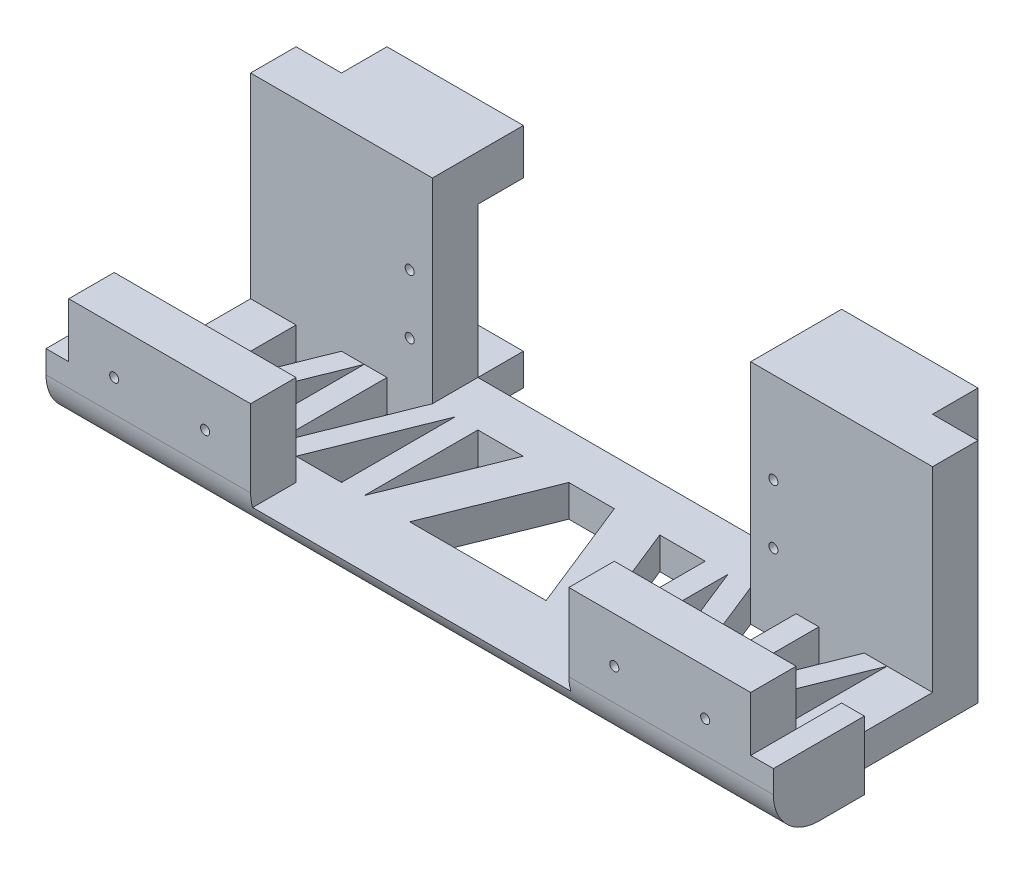
SolidWorks part; units mm, degrees
ref_plane "Plan de face" through (0, 0, 0) normal (0, 0, 1) x (1, 0, 0)
ref_plane "Plan de dessus" through (0, 0, 0) normal (0, 1, 0) x (1, 0, 0)
ref_plane "Plan de droite" through (0, 0, 0) normal (1, 0, 0) x (0, 0, -1)
sketch "Esquisse2" plane through (0, 0, 0) normal (0, 0, 1) x (1, 0, 0)
  line L0 (-161.1414, -90.4642) -> (-121.1414, -90.4642)
  line L1 (-161.1414, -90.4642) -> (-161.1414, -140.4642)
  line L2 (-121.1414, -90.4642) -> (-121.1414, -140.4642)
  line L3 (-161.1414, -140.4642) -> (-121.1414, -140.4642)
  line L4 (-121.1414, 19.5358) -> (-121.1414, -100.4642) construction
  line L5 (-11.1414, -90.4642) -> (-51.1414, -90.4642)
  line L6 (-11.1414, -90.4642) -> (-11.1414, -140.4642)
  line L7 (-51.1414, -90.4642) -> (-51.1414, -140.4642)
  line L8 (-11.1414, -140.4642) -> (-51.1414, -140.4642)
  line L9 (-51.1414, 19.5358) -> (-51.1414, -100.4642) construction
  line L11 (-121.1414, -133.4642) -> (-51.1414, -133.4642)
  line L12 (-121.1414, -140.4642) -> (-51.1414, -140.4642)
  line L13 (-51.1414, -133.4642) -> (-51.1414, -140.4642)
  line L14 (-136.1414, -133.4642) -> (-36.1414, -133.4642) construction
  line L15 (-21.1414, -140.4642) -> (-11.1414, -140.4642) construction
  line L16 (-151.1414, -90.4642) -> (-171.1414, -90.4642) construction
  line L17 (-1.1414, -90.4642) -> (-21.1414, -90.4642) construction
  line M10 (-51.1414, -100.4642) -> (-51.1414, 19.5358)
  line M16 (-121.1414, 19.5358) -> (-121.1414, -100.4642)
  line M17 (-121.1414, -100.4642) -> (-136.1414, -100.4642)
  line M18 (-136.1414, -100.4642) -> (-136.1414, -133.4642)
  line M19 (-136.1414, -133.4642) -> (-36.1414, -133.4642)
  line M20 (-36.1414, -133.4642) -> (-36.1414, -100.4642)
  line M21 (-36.1414, -100.4642) -> (-51.1414, -100.4642)
  circle M38 centre (-46.1414, -123.4642) radius 1
  circle M39 centre (-46.1414, -110.4642) radius 1
  circle M42 centre (-126.1414, -123.4642) radius 1
  circle M45 centre (-126.1414, -110.4642) radius 1
extrude "Boss.-Extru.1" add sketch "Esquisse2" along normal blind 10 contours L1 L3 L2 L0 M19 M18 M17 M16 | L2 M17 M18 M19 M42 M45 | L13 L2 L12 M19 | L7 M21 M19 M20 M38 M39 | L8 L6 L5 L7 M10 M21 M20 M19 region at (-145.2527, -114.9708, 0) region at (-128.6736, -116.9642, 0) region at (-86.1414, -136.9642, 0) region at (-27.0301, -114.9708, 0) region at (-43.6093, -116.9642, 0)
sketch "Esquisse3" plane through (0, 0, 10) normal (0, 0, 1) x (1, 0, 0)
  line L0 (-161.1414, -140.4642) -> (-161.1414, -133.4642)
  line L1 (-161.1414, -140.4642) -> (-11.1414, -140.4642)
  line L2 (-161.1414, -133.4642) -> (-11.1414, -133.4642)
  line L3 (-11.1414, -140.4642) -> (-11.1414, -133.4642)
  line L5 (-11.1414, -90.4642) -> (-11.1414, -140.4642) construction
  line L6 (-121.1414, -133.4642) -> (-51.1414, -133.4642) construction
  line L7 (-161.1414, -90.4642) -> (-161.1414, -140.4642) construction
  line L8 (-226.1414, -140.4642) -> (-161.1414, -140.4642) construction
extrude "Boss.-Extru.2" add sketch "Esquisse3" along normal blind 40
sketch "Esquisse4" plane through (0, 0, 50) normal (0, 0, 1) x (1, 0, 0)
  line L0 (-161.1414, -133.4642) -> (-161.1414, -113.4642)
  line L1 (-161.1414, -133.4642) -> (-121.1414, -133.4642)
  line L2 (-161.1414, -113.4642) -> (-121.1414, -113.4642)
  line L3 (-121.1414, -133.4642) -> (-121.1414, -113.4642)
  line L4 (-11.1414, -133.4642) -> (-11.1414, -113.4642)
  line L5 (-11.1414, -133.4642) -> (-51.1414, -133.4642)
  line L6 (-11.1414, -113.4642) -> (-51.1414, -113.4642)
  line L7 (-51.1414, -133.4642) -> (-51.1414, -113.4642)
  line L8 (-161.1414, -140.4642) -> (-161.1414, -125.4642)
  line L9 (-161.1414, -140.4642) -> (-166.1414, -140.4642)
  line L10 (-161.1414, -125.4642) -> (-166.1414, -125.4642)
  line L11 (-166.1414, -140.4642) -> (-166.1414, -125.4642)
  line L12 (-11.1414, -140.4642) -> (-11.1414, -125.4642)
  line L13 (-11.1414, -140.4642) -> (-6.1414, -140.4642)
  line L14 (-11.1414, -125.4642) -> (-6.1414, -125.4642)
  line L15 (-6.1414, -140.4642) -> (-6.1414, -125.4642)
  circle A0 centre (-151.1414, -123.4642) radius 1
  circle A1 centre (-131.1414, -123.4642) radius 1
  circle A2 centre (-41.1414, -123.4642) radius 1
  circle A3 centre (-21.1414, -123.4642) radius 1
  line M10 (-11.1414, -140.4642) -> (-11.1414, -133.4642)
  line M11 (-11.1414, -133.4642) -> (-161.1414, -133.4642)
  line M12 (-161.1414, -133.4642) -> (-161.1414, -140.4642)
  dimension "D13" = 2
  dimension "D14" = 2
  dimension "D19" = 2
  dimension "D20" = 2
  dimension "D1" = 40
  dimension "D2" = 20
  dimension "D3" = 40
  dimension "D4" = 20
  dimension "D5" = 15
  dimension "D6" = 5
  dimension "D7" = 15
  dimension "D8" = 5
  dimension "D9" = 10
  dimension "D10" = 10
  dimension "D11" = 10
  dimension "D12" = 10
  dimension "D15" = 10
  dimension "D16" = 10
  dimension "D17" = 10
  dimension "D18" = 10
extrude "Boss.-Extru.3" add sketch "Esquisse4" against normal blind 20 contours L7 L4 L6 M11 | L13 L15 L14 L4 M10 | L11 L9 L0 L10 M12 | L3 L2 L0 M11 region at (-163.6414, -132.9642, 50) region at (-141.1414, -123.4642, 50) region at (-31.1414, -123.4642, 50) region at (-8.6414, -132.9642, 50)
sketch "Esquisse5" plane through (0, -140.4642, 0) normal (0, -1, 0) x (1, 0, 0)
  line L18 (-151.1414, 35) -> (-151.1414, 10)
  line L19 (-151.1414, 10) -> (-141.1414, 10)
  line L20 (-141.1414, 10) -> (-151.1414, 35)
  line L21 (-146.1414, 35) -> (-136.1414, 10)
  line L22 (-136.1414, 10) -> (-136.1414, 35)
  line L23 (-136.1414, 35) -> (-146.1414, 35)
  line L24 (-131.1414, 35) -> (-131.1414, 10)
  line L25 (-131.1414, 10) -> (-121.1414, 10)
  line L26 (-121.1414, 10) -> (-131.1414, 35)
  line L27 (-126.1414, 35) -> (-116.1414, 10)
  line L28 (-161.1414, 30) -> (-161.1414, 0) construction
  line L29 (-166.1414, 50) -> (-6.1414, 50) construction
  line L30 (-101.1414, 35) -> (-91.1414, 10)
  line L31 (-41.1414, 35) -> (-36.1414, 35) construction
  line L32 (-116.1414, 10) -> (-116.1414, 35)
  line L33 (-116.1414, 35) -> (-126.1414, 35)
  line L34 (-111.1414, 35) -> (-111.1414, 10)
  line L35 (-111.1414, 10) -> (-101.1414, 10)
  line L36 (-101.1414, 10) -> (-111.1414, 35)
  line L37 (-71.1414, 10) -> (-61.1414, 10)
  line L38 (-61.1414, 10) -> (-61.1414, 35)
  line L39 (-36.1414, 35) -> (-31.1414, 35) construction
  line L40 (-71.1414, 10) -> (-61.1414, 35)
  line L41 (-46.1414, 35) -> (-56.1414, 35)
  line L42 (-56.1414, 35) -> (-56.1414, 10)
  line L43 (-56.1414, 10) -> (-46.1414, 35)
  line L44 (-41.1414, 35) -> (-51.1414, 10)
  line L45 (-51.1414, 10) -> (-41.1414, 10)
  line L46 (-41.1414, 10) -> (-41.1414, 35)
  line L47 (-21.1414, 35) -> (-21.1414, 10)
  line L48 (-21.1414, 10) -> (-31.1414, 35)
  line L49 (-31.1414, 35) -> (-21.1414, 35)
  line L50 (-36.1414, 35) -> (-36.1414, 10)
  line L51 (-36.1414, 10) -> (-26.1414, 10)
  line L52 (-26.1414, 10) -> (-36.1414, 35)
  line L53 (-151.1414, 35) -> (-146.1414, 35) construction
  line L54 (-136.1414, 35) -> (-131.1414, 35) construction
  line L55 (-131.1414, 35) -> (-126.1414, 35) construction
  line L56 (-41.1414, 10) -> (-36.1414, 10) construction
  line L57 (-46.1414, 35) -> (-41.1414, 35) construction
  line L58 (-61.1414, 35) -> (-56.1414, 35) construction
  line L59 (-61.1414, 10) -> (-56.1414, 10) construction
  line L60 (-56.1414, 10) -> (-51.1414, 10) construction
  line L61 (-11.1414, 30) -> (-11.1414, 0) construction
  line L62 (-21.1414, 10) -> (-26.1414, 10) construction
  line L63 (-111.1414, 35) -> (-116.1414, 35) construction
  line L64 (-111.1414, 10) -> (-116.1414, 10) construction
  line L65 (-121.1414, 10) -> (-116.1414, 10) construction
  line L66 (-136.1414, 10) -> (-131.1414, 10) construction
  line L67 (-141.1414, 10) -> (-136.1414, 10) construction
  line L68 (-161.1414, 0) -> (-11.1414, 0) construction
  line L69 (-91.1414, 10) -> (-81.1414, 10)
  line L70 (-81.1414, 10) -> (-71.1414, 35)
  line L71 (-71.1414, 35) -> (-101.1414, 35)
  dimension "D1" = 10
  dimension "D2" = 15
  dimension "D3" = 15
  dimension "D4" = 10
  dimension "D5" = 10
  dimension "D6" = 10
  dimension "D7" = 5
  dimension "D8" = 10
  dimension "D9" = 10
  dimension "D10" = 10
  dimension "D11" = 10
  dimension "D12" = 10
extrude "Enlèv. mat.-Extru.1" cut sketch "Esquisse5" against normal through all contours L20 L18 L19 | L23 L21 L22 | L26 L24 L25 | L33 L27 L32 | L34 L35 L36 | L71 L30 L69 L70 | L38 L37 L40 | L41 L42 L43 | L44 L45 L46 | L52 L50 L51 | L47 L48 L49
sketch "Esquisse6" plane through (0, 0, 30) normal (0, 0, -1) x (-1, 0, 0)
  line L0 (11.1414, -113.4642) -> (11.1414, -133.4642)
  line L1 (11.1414, -113.4642) -> (51.1414, -113.4642)
  line L2 (11.1414, -133.4642) -> (51.1414, -133.4642)
  line L3 (51.1414, -113.4642) -> (51.1414, -133.4642)
  line L4 (11.1414, -90.4642) -> (11.1414, -140.4642) construction
  line L6 (121.1414, -133.4642) -> (161.1414, -133.4642)
  line L7 (121.1414, -133.4642) -> (121.1414, -113.4642)
  line L8 (161.1414, -133.4642) -> (161.1414, -113.4642)
  line L9 (121.1414, -113.4642) -> (161.1414, -113.4642)
  line L10 (161.1414, -90.4642) -> (161.1414, -140.4642) construction
  line L11 (121.1414, -133.4642) -> (51.1414, -133.4642) construction
  line L12 (51.1414, -133.4642) -> (51.1414, -90.4642) construction
extrude "Enlèv. mat.-Extru.2" cut sketch "Esquisse6" against normal blind 10
fillet "Congé1" radius 10 1 edges at (-86.1414, -140.4642, 50)
sketch "Esquisse7" plane through (0, 0, 0) normal (0, 0, -1) x (-1, 0, 0)
  line L0 (51.1414, -90.4642) -> (51.1414, -140.4642)
  line L1 (51.1414, -90.4642) -> (21.1414, -90.4642)
  line L2 (51.1414, -140.4642) -> (21.1414, -140.4642)
  line L3 (21.1414, -90.4642) -> (21.1414, -140.4642)
  line L4 (121.1414, -90.4642) -> (121.1414, -140.4642)
  line L5 (121.1414, -90.4642) -> (151.1414, -90.4642)
  line L6 (121.1414, -140.4642) -> (151.1414, -140.4642)
  line L7 (151.1414, -90.4642) -> (151.1414, -140.4642)
  line L8 (121.1414, -100.4642) -> (136.1414, -100.4642)
  line L9 (121.1414, -100.4642) -> (121.1414, -133.4642)
  line L10 (136.1414, -100.4642) -> (136.1414, -133.4642)
  line L11 (121.1414, -133.4642) -> (136.1414, -133.4642)
  line L12 (121.1414, -90.4642) -> (121.1414, -133.4642) construction
  line L15 (36.1414, -133.4642) -> (51.1414, -133.4642)
  line L16 (36.1414, -133.4642) -> (36.1414, -100.4642)
  line L17 (51.1414, -133.4642) -> (51.1414, -100.4642)
  line L18 (36.1414, -100.4642) -> (51.1414, -100.4642)
  line L19 (21.1414, -90.4642) -> (21.1414, -140.4642) construction
  line L20 (161.1414, -140.4642) -> (11.1414, -140.4642) construction
  line L21 (161.1414, -90.4642) -> (121.1414, -90.4642) construction
  line L22 (51.1414, -100.4642) -> (36.1414, -100.4642) construction
  line L23 (36.1414, -100.4642) -> (36.1414, -133.4642) construction
  line L24 (151.1414, -90.4642) -> (151.1414, -140.4642) construction
  line M4 (51.1414, -90.4642) -> (11.1414, -90.4642)
  line M6 (11.1414, -140.4642) -> (161.1414, -140.4642)
  line M8 (161.1414, -90.4642) -> (121.1414, -90.4642)
  line M9 (121.1414, -90.4642) -> (121.1414, -133.4642)
extrude "Boss.-Extru.4" add sketch "Esquisse7" along normal blind 10 contours L16 L18 L0 L3 L15 M4 M6 | L11 L4 L7 L8 L10 M6 M8 M9 region at (-139.8355, -114.7254, 0) region at (-32.4474, -114.7254, 0)
